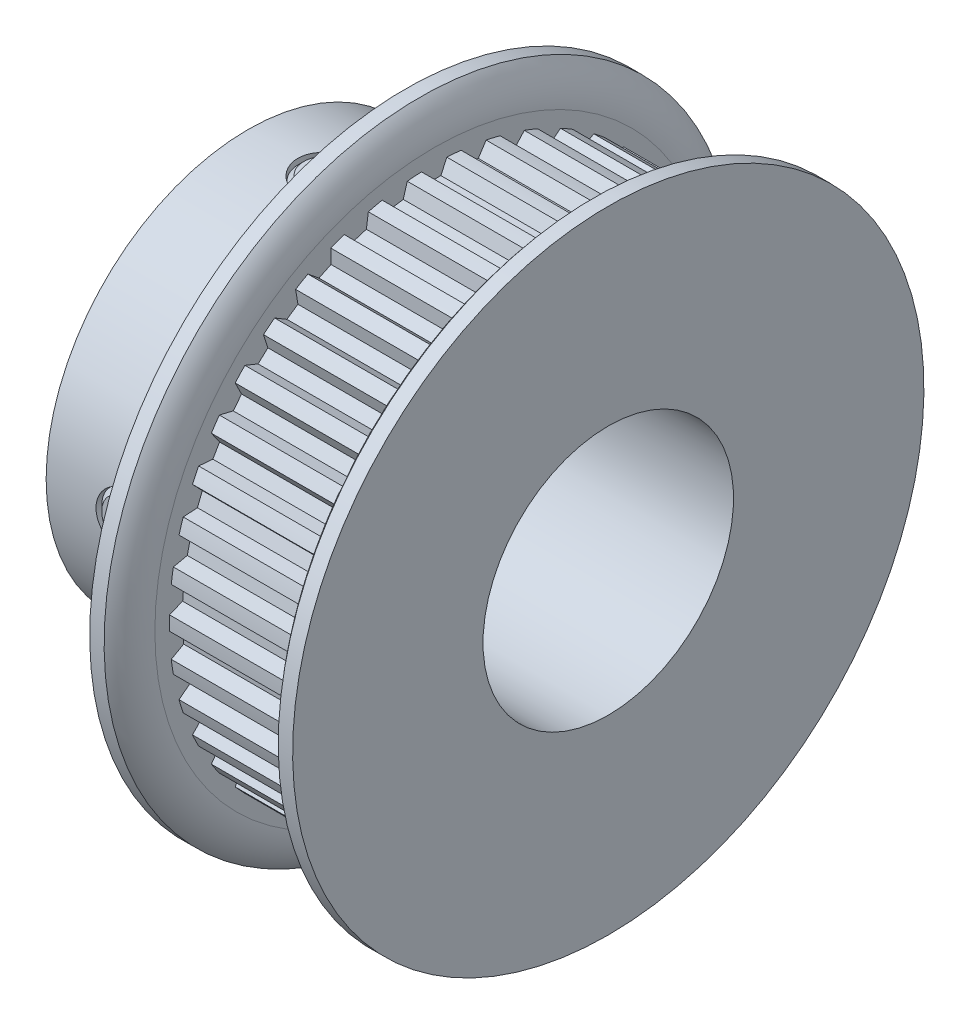
SolidWorks part; units mm, degrees
ref_plane "Front Plane" through (0, 0, 0) normal (0, 0, 1) x (1, 0, 0)
ref_plane "Top Plane" through (0, 0, 0) normal (0, 1, 0) x (1, 0, 0)
ref_plane "Right Plane" through (0, 0, 0) normal (1, 0, 0) x (0, 0, -1)
sketch "Sketch2" plane through (0, 0, 0) normal (1, 0, 0) x (0, 0, -1)
  line L3 (0, 0) -> (0, 12.7635) construction
  line L6 (0, -13.2715) -> (0, -13.589) construction
  line L7 (-0.5715, 13.2592) -> (-0.3383, 12.759)
  line L8 (0.5715, 13.2592) -> (0.3383, 12.759)
  line L9 (-0.5715, 13.2592) -> (-0.6441, 13.4148)
  line L10 (0.5715, 13.2592) -> (0.6441, 13.4148)
  line L12 (-0.3383, 12.759) -> (0.3383, 12.759)
  line L14 (0, 13.2715) -> (0, 13.589) construction
  line L15 (0, 0) -> (0, -1.143) construction
  circle A0 centre (0, 0) radius 13.589 construction
  circle A1 centre (0, 0) radius 12.7635 construction
  circle A2 centre (0, 0) radius 13.2715 construction
  arc A7 (0.6441, 13.4148) -> (-0.6441, 13.4148) centre (0, 0) ccw
  point P5 (0, 13.4303)
  dimension "D3" = 0.3175
  dimension "D1" = 50
sketch "Sketch1" plane through (0, 0, 0) normal (0, 0, 1) x (1, 0, 0)
  line L0 (-9.1313, 0) -> (9.1313, 0) construction
  line L1 (-9.1313, 3.175) -> (9.1313, 3.175)
  line L2 (-9.1313, 3.175) -> (-9.1313, 10.2362)
  line L3 (-1.1557, 16.002) -> (-0.4254, 16.002)
  line L4 (0.3048, 13.589) -> (0.3048, 14.1605)
  line L5 (0.3048, 14.732) -> (0.3048, 13.589) construction
  line L6 (0.3048, 13.589) -> (7.6708, 13.589)
  line L7 (7.6708, 13.589) -> (7.6708, 14.1605)
  line L8 (7.6708, 13.589) -> (9.1313, 13.589) construction
  line L9 (8.4011, 16.002) -> (9.1313, 16.002)
  line L10 (9.1313, 16.002) -> (9.1313, 3.175)
  line L11 (8.4011, 13.589) -> (8.4011, 16.002) construction
  line L12 (-5.1435, 10.2362) -> (-5.1435, 3.175) construction
  line L13 (-1.1557, 16.002) -> (-1.1557, 10.2362)
  line L14 (-1.1557, 10.2362) -> (-9.1313, 10.2362)
  arc A0 (7.6708, 14.1605) -> (8.4011, 16.002) centre (10.3578, 14.1605) cw
  arc A1 (0.3048, 14.1605) -> (-0.4254, 16.002) centre (-2.3822, 14.1605) ccw
  dimension "Bore Size" = 6.35
  dimension "Overall Width" = 18.2626
  dimension "Inside Width" = 7.366
  dimension "OD" = 32.004
  dimension "D2" = 27.178
  dimension "D3" = 1.143
  dimension "D4" = 0.5715
  dimension "Outside Width" = 10.287
revolve "Revolve1" add sketch "Sketch1" angle 360 mid plane about L0
sketch "Sketch4" plane through (0.3048, 0, 0) normal (1, 0, 0) x (0, 0, -1)
  circle A0 centre (0, 0) radius 13.4303
  circle A2 centre (0, 0) radius 13.589
  circle A3 centre (0, 0) radius 13.589 construction
extrude "Cut-Extrude2" cut sketch "Sketch4" along normal up to surface (7.366 mm away) up to face at (7.6708, -13.589, 0)
sketch "Sketch3" plane through (0.3048, 0, 0) normal (1, 0, 0) x (0, 0, -1)
  line L2 (-0.5715, 13.2592) -> (-0.3383, 12.759) construction
  line L3 (-0.3383, 12.759) -> (0.3383, 12.759) construction
  line L4 (0.5715, 13.2592) -> (0.3383, 12.759) construction
  line L5 (-0.6441, 13.4148) -> (-0.3383, 12.759)
  line L6 (-0.3383, 12.759) -> (0.3383, 12.759)
  line L7 (0.6441, 13.4148) -> (0.3383, 12.759)
  arc A1 (0.6441, 13.4148) -> (-0.6441, 13.4148) centre (0, 0) ccw construction
  arc A2 (0.6441, 13.4148) -> (-0.6441, 13.4148) centre (0, 0) ccw
extrude "Cut-Extrude1" cut sketch "Sketch3" along normal up to surface (7.366 mm away) up to face at (7.6708, -14.1605, 0)
pattern_circular "CirPattern1" count 42 over 360 of "Cut-Extrude1"
sketch "Sketch5" plane through (0, 0, 0) normal (0, 0, 1) x (1, 0, 0)
  line L1 (7.6708, 14.1605) -> (7.6708, -14.1605) construction
  point P0 (7.6708, 0)
sketch "Sketch6" plane through (0, 0, 0) normal (0, 1, 0) x (1, 0, 0)
  line L0 (-9.1313, 0) -> (-6.604, 0) construction
  line L1 (-9.1313, 16.002) -> (-9.1313, -16.002) construction
  line L2 (-1.1557, 0) -> (-3.683, 0) construction
  line L4 (-1.1557, 16.002) -> (-1.1557, -16.002) construction
  circle A0 centre (-5.1435, 0) radius 1.4605
  dimension "D1" = 2.921
extrude "Cut-Extrude3" cut sketch "Sketch6" along normal through all
sketch "Sketch7" plane through (0, 0, 0) normal (0, 0, 1) x (1, 0, 0)
  line L0 (-6.3119, 10.2362) -> (-5.1435, 10.2362)
  line L1 (-6.5659, 9.9822) -> (-6.5659, 3.81)
  line L2 (-6.5659, 3.81) -> (-6.3119, 3.556)
  line L3 (-6.3119, 3.556) -> (-5.1435, 3.556)
  line L4 (-5.1435, 3.556) -> (-5.1435, 10.2362) construction
  line L5 (-1.1557, 10.2362) -> (-9.1313, 10.2362) construction
  line L6 (-6.5659, 9.9822) -> (-6.3119, 10.2362)
  line L8 (-5.1435, 10.2362) -> (-5.1435, 3.556)
  point P0 (-6.5659, 10.2362)
  point P4 (-6.5659, 3.556)
  dimension "D1" = 2.8448
  dimension "D2" = 0.381
revolve "Revolve2" add sketch "Sketch7" angle 360 mid plane about L4
sketch "Sketch8" plane through (0, 10.2362, 0) normal (0, 1, 0) x (1, 0, 0)
  line L1 (-5.1435, 0.8212) -> (-5.8547, 0.4106)
  line L2 (-5.8547, 0.4106) -> (-5.8547, -0.4106)
  line L3 (-5.8547, -0.4106) -> (-5.1435, -0.8212)
  line L4 (-5.1435, -0.8212) -> (-4.4323, -0.4106)
  line L5 (-4.4323, -0.4106) -> (-4.4323, 0.4106)
  line L6 (-4.4323, 0.4106) -> (-5.1435, 0.8212)
  circle A0 centre (-5.1435, 0) radius 0.7112 construction
  dimension "D1" = 1.4224
extrude "Cut-Extrude4" cut sketch "Sketch8" against normal blind 1.016
pattern_circular "CirPattern2" count 2 over 90 about axis through (-9.1313, 0, 0) along (-1, 0, 0) of "Cut-Extrude3" reverse direction yes
pattern_circular "CirPattern3" count 2 over 90 reverse direction yes of bodies 107
sketch "Sketch9" plane through (-9.1313, 0, 0) normal (-1, 0, 0) x (0, 0, 1)
  circle A0 centre (0, 0) radius 6.35
  dimension "D1" = 12.7
extrude "Cut-Extrude6" cut sketch "Sketch9" along normal blind 2.54 and the other way through all
equation "\"D3@Sketch2\" = (\"hs@Sketch2\"-\"ht@Sketch2\")/2"
equation "\"D2@Sketch1\" = \"PD@Sketch2\""
equation "\"D3@Sketch1\" = \"hs@Sketch2\""
equation "\"D4@Sketch1\" = \"D3@Sketch1\"/2"
